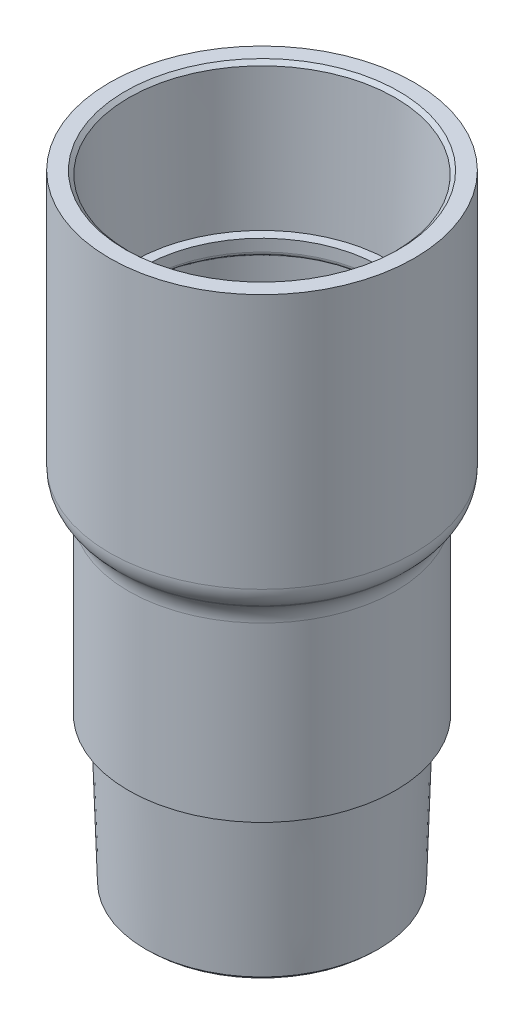
SolidWorks part; units mm, degrees
material "Brass"
ref_plane "Front Plane" through (0, 0, 0) normal (0, 0, 1) x (1, 0, 0)
ref_plane "Top Plane" through (0, 0, 0) normal (0, 1, 0) x (1, 0, 0)
ref_plane "Right Plane" through (0, 0, 0) normal (1, 0, 0) x (0, 0, -1)
sketch "Sketch3" plane through (0, 0, 0) normal (0, 0, 1) x (1, 0, 0)
  line L0 (15.4305, 23.7794) -> (15.4305, 41.275)
  line L1 (12.7, 0) -> (12.7, 19.05)
  line L2 (12.7, 19.05) -> (15.4305, 23.7794)
  line L3 (15.4305, 41.275) -> (15.875, 41.275)
  line L4 (0, 0) -> (0, 82.55) construction
  line L5 (15.875, 41.275) -> (15.875, 47.3075)
  line L6 (15.875, 63.5) -> (17.145, 63.5)
  line L7 (17.145, 63.5) -> (17.7405, 82.55)
  line L8 (17.7405, 82.55) -> (20.2805, 82.55)
  line L9 (20.2805, 82.55) -> (20.2805, 44.45)
  line L10 (20.2805, 44.45) -> (17.78, 44.45)
  line L11 (17.78, 44.45) -> (17.78, 19.9227)
  line L14 (15.4781, 0) -> (12.7, 0)
  line L15 (15.4781, 0) -> (16.0736, 19.05)
  line L17 (16.0736, 19.05) -> (16.3276, 19.05)
  line L18 (16.3276, 19.05) -> (17.78, 19.9227)
  line L19 (15.875, 61.2775) -> (17.145, 61.2775)
  line L20 (17.145, 61.2775) -> (17.145, 47.3075)
  line L21 (17.145, 47.3075) -> (15.875, 47.3075)
  line L22 (15.875, 61.2775) -> (15.875, 63.5)
  point P20 (0, 0)
  point P23 (15.875, 45.4471)
  dimension "D1" = 25.4
  dimension "D2" = 30
  dimension "D3" = 19.05
  dimension "D4" = 1.791
  dimension "D5" = 30.9562
  dimension "D6" = 0.4445
  dimension "D7" = 41.275
  dimension "D8" = 44.45
  dimension "D9" = 1.791
  dimension "D10" = 19.05
  dimension "D11" = 1.27
  dimension "D12" = 2.54
  dimension "D13" = 19.05
  dimension "D14" = 1.905
  dimension "D15" = 31.75
  dimension "D16" = 82.55
  dimension "D17" = 59
  dimension "D18" = 0.254
  dimension "D19" = 13.97
  dimension "D20" = 2.8575
  dimension "D21" = 1.27
revolve "Revolve1" add sketch "Sketch3" angle 360 about L4
ref_axis "Centerline" through (0, 41.275, 0) along (0, -1, 0)
sketch "Sketch5" plane through (0, 0, 0) normal (0, 0, 1) x (1, 0, 0)
  line L0 (15.875, 41.275) -> (-15.875, 41.275) construction
  line L1 (0, 41.275) -> (0, 23.7794) construction
  circle A0 centre (-12.065, 38.4175) radius 1.5875
  point P2 (-9.8968, 37.7607)
  point P7 (-15.2941, 38.1203)
  point P8 (-10.2015, 37.8754)
  dimension "D1" = 2.8575
  dimension "D3" = 3.175
  dimension "D2" = 12.065
extrude "Fuel-Inlet" cut sketch "Sketch5" against normal blind 10.8458
pattern_circular "Fuel-Inlet_Pattern" count 4 over 360 about axis through (0, 0, 0) along (0, -1, 0) of "Fuel-Inlet" reverse direction yes
chamfer "Thread_Prep" distance 0.4762 angle 45 2 edges at (0, 82.55, -17.7405) (0, 0, -15.4781) first distance on face at (0, 63.5, -17.145) first distance on face at (0, 19.05, -16.0736)
sketch "Sketch7" [suppressed] plane through (0, 19.05, 0) normal (0, -1, 0) x (1, 0, 0)
  circle A1 centre (0, 0) radius 16.0736
  circle A2 centre (0, 0) radius 16.0736
  dimension "D1" = 0
curve "Helix/Spiral1" [suppressed]
sketch "Sketch9" [suppressed] plane through (0, 0, 0) normal (0, 0, 1) x (1, 0, 0)
  line L0 (15.4781, 0) -> (15.493, 0.476) construction
  line L1 (-14.9863, 0) -> (14.9863, 0) construction
  line L2 (0, 41.275) -> (0, 23.7794) construction
  line L3 (-14.9863, 0) -> (14.9863, 0) construction
  line L4 (-15.493, 0.476) -> (15.493, 0.476) construction
  line L5 (-15.493, 0.476) -> (15.493, 0.476) construction
  line L6 (14.9863, 0) -> (15.4781, 0) construction
  line L8 (15.7172, 0.138) -> (14.0435, -0.8283)
  line L10 (14.0435, -1.1043) -> (14.0435, -0.8283)
  line L11 (13.8044, -0.9663) -> (14.0435, -0.9663) construction
  line L12 (13.8044, -0.9663) -> (15.7172, 0.138) construction
  line L13 (14.0435, -1.1043) -> (15.5977, -2.0016)
  line L14 (15.4781, 0) -> (15.4781, -1.9326) construction
  line L15 (15.7172, 0.138) -> (15.7172, -2.0707) construction
  line L16 (15.7172, 0.138) -> (15.5977, -2.0016)
  line L17 (15.5977, -2.0016) -> (15.5977, -0.9663) construction
  line L18 (15.4781, -0.9663) -> (15.7172, -0.9663) construction
  line L19 (13.8044, -0.9663) -> (15.7172, -2.0707) construction
  point P18 (14.2831, -2.028)
  point P19 (15.4781, -0.9663)
  point P20 (15.7172, -0.9663)
  dimension "D1" = 2.2087
  dimension "D2" = 181.791
  dimension "D3" = 0.2761
sweep "Cut-Sweep1" [suppressed] cut profiles "Sketch9" path "Helix/Spiral1"
sketch "Sketch10" [suppressed] plane through (0, 82.55, 0) normal (0, 1, 0) x (1, 0, 0)
  circle A0 centre (0, 0) radius 17.7256 construction
  circle A1 centre (0, 0) radius 17.7256
curve "Helix/Spiral2" [suppressed]
sketch "Sketch11" [suppressed] plane through (0, 0, 0) normal (0, 0, 1) x (1, 0, 0)
  line L0 (-17.7256, 82.074) -> (-17.7405, 82.55) construction
  line L1 (-17.7256, 82.074) -> (17.7256, 82.074) construction
  line L2 (-17.7256, 82.074) -> (17.7256, 82.074) construction
  line L3 (18.2324, 82.55) -> (-18.2324, 82.55) construction
  line L4 (18.2324, 82.55) -> (-18.2324, 82.55) construction
  line L6 (-17.6897, 82.55) -> (-17.6897, 84.7587) construction
  line L7 (-17.6897, 84.7587) -> (-19.6025, 83.6543) construction
  line L8 (-19.6025, 83.6543) -> (-17.6897, 82.55) construction
  line L9 (-17.8093, 84.6897) -> (-17.8093, 83.6543) construction
  line L10 (-17.9288, 84.6207) -> (-17.9288, 82.688) construction
  line L11 (-17.9288, 83.6543) -> (-17.6897, 83.6543) construction
  line L12 (-19.3634, 83.7924) -> (-19.3634, 83.5163)
  line L13 (-19.3634, 83.6543) -> (-19.6025, 83.6543) construction
  line L14 (-19.3634, 83.7924) -> (-17.8093, 84.6897)
  line L15 (-17.8093, 84.6897) -> (-17.6897, 82.55)
  line L16 (-17.6897, 82.55) -> (-19.3634, 83.5163)
  line L17 (0, 41.275) -> (0, 23.7794) construction
  dimension "D1" = 1.791
  dimension "D2" = 2.2087
  dimension "D3" = 0.2761
  dimension "D4" = 0.0508
sweep "Cut-Sweep8" [suppressed] cut profiles "Sketch11" path "Helix/Spiral2"
chamfer "Outside Prep Round" distance 2.54 angle 45 1 edges at (0, 44.45, -20.2805)
fillet "Outer Round" radius 3.81 2 edges at (0, 46.99, -20.2805) (0, 44.4895, 17.78)
fillet "Inside Round" radius 8.89 2 edges at (0, 23.7794, -15.4305) (0, 19.05, -12.7)
fillet "Step Round" radius 0.127 1 edges at (0, 41.275, -15.875)
fillet "Groove Rounds" radius 0.635 4 edges at (0, 61.2775, -15.875) (0, 61.2775, -17.145) (0, 47.3075, -17.145) (0, 47.3075, -15.875)
fillet "Exit Round" radius 0.8255 1 edges at (0, 0, -12.7)
